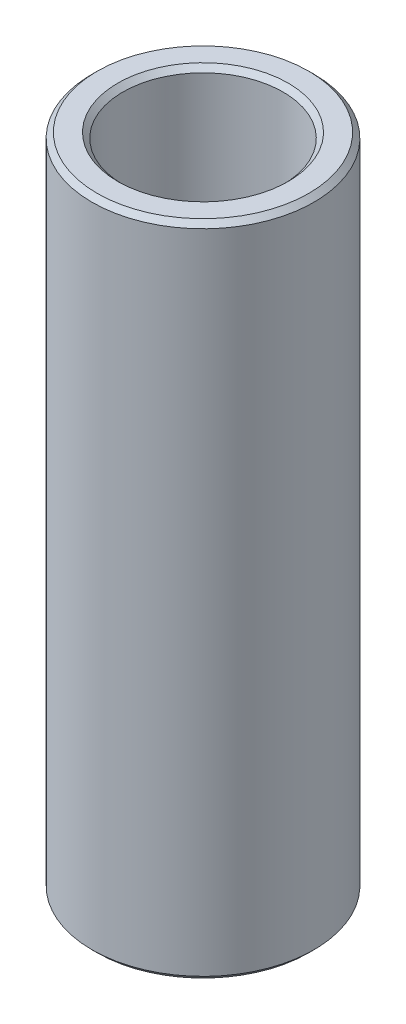
SolidWorks part; units mm, degrees
ref_plane "Front Plane" through (0, 0, 0) normal (0, 0, 1) x (1, 0, 0)
ref_plane "Top Plane" through (0, 0, 0) normal (0, 1, 0) x (1, 0, 0)
ref_plane "Right Plane" through (0, 0, 0) normal (1, 0, 0) x (0, 0, -1)
sketch "Sketch1" plane through (0, 0, 0) normal (0, 1, 0) x (1, 0, 0)
  circle A0 centre (0, 0) radius 12.5
  dimension "SLEEVE_OD" = 25
extrude "Boss-Extrude1" add sketch "Sketch1" along normal blind 74.0945
sketch "Sketch2" plane through (0, 0, 0) normal (0, 1, 0) x (1, 0, 0)
  circle A0 centre (0, 0) radius 9.0261
  dimension "BORE_D" = 18.0523
extrude "Cut-Extrude1" cut sketch "Sketch2" along normal through all
chamfer "Chamfer1" distance 0.5773 angle 45 4 edges at (0, 74.0945, 9.0261) (0, 0, 9.0261) (0, 0, 12.5) (0, 74.0945, 12.5)
